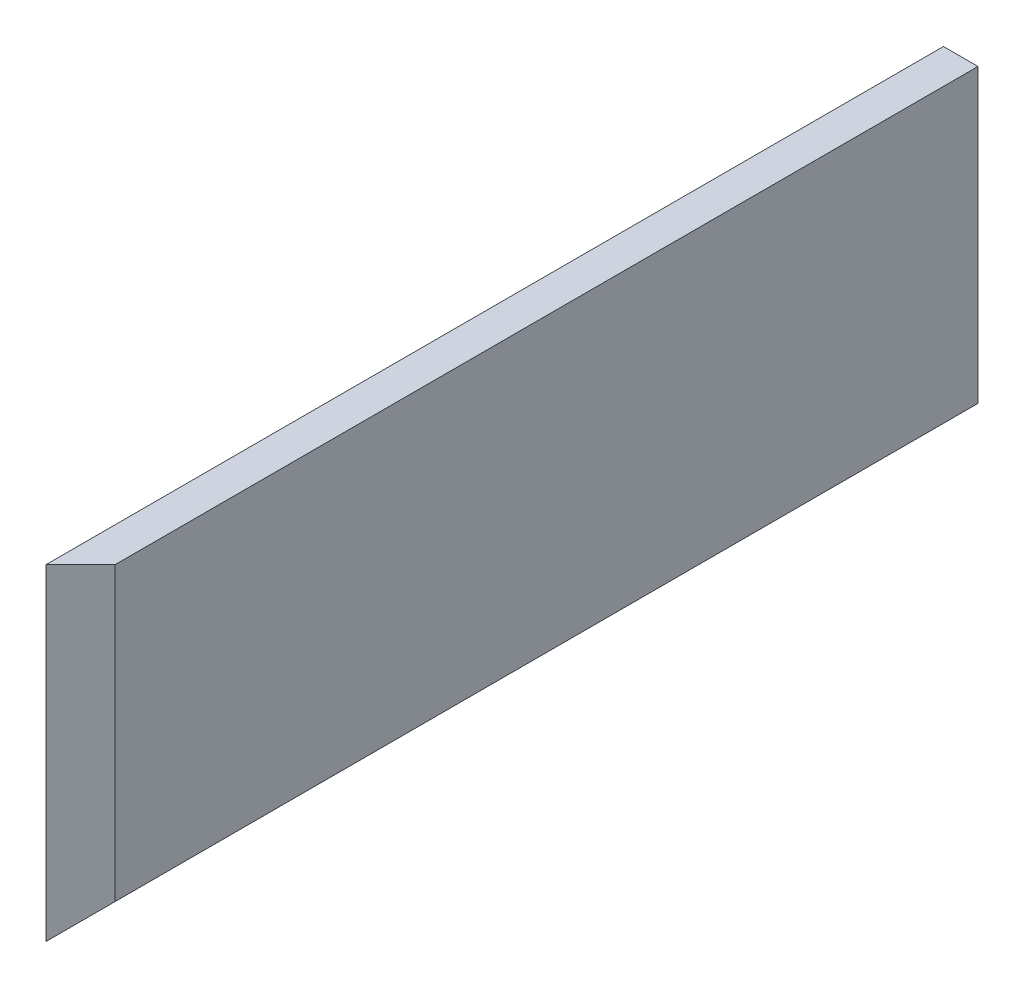
SolidWorks part; units mm, degrees
ref_plane "Front Plane" through (0, 0, 0) normal (0, 0, 1) x (1, 0, 0)
ref_plane "Top Plane" through (0, 0, 0) normal (0, 1, 0) x (1, 0, 0)
ref_plane "Right Plane" through (0, 0, 0) normal (1, 0, 0) x (0, 0, -1)
sketch "Sketch1" plane through (0, 0, 0) normal (1, 0, 0) x (0, 0, -1)
  line L1 (165, -60) -> (-165, -60)
  line L2 (165, -60) -> (165, 60)
  line L3 (165, 60) -> (-165, 60)
  line L4 (-165, -60) -> (-165, 60)
  line L5 (165, -60) -> (-165, 60) construction
  line L6 (165, 60) -> (-165, -60) construction
  point P0 (0, 0)
  dimension "D1" = 120
  dimension "D2" = 330
extrude "Boss-Extrude1" add sketch "Sketch1" along normal blind 12.7
chamfer "Chamfer1" distance 12.7 angle 45 2 edges at (12.7, 0, 165) (12.7, -60, 0)
